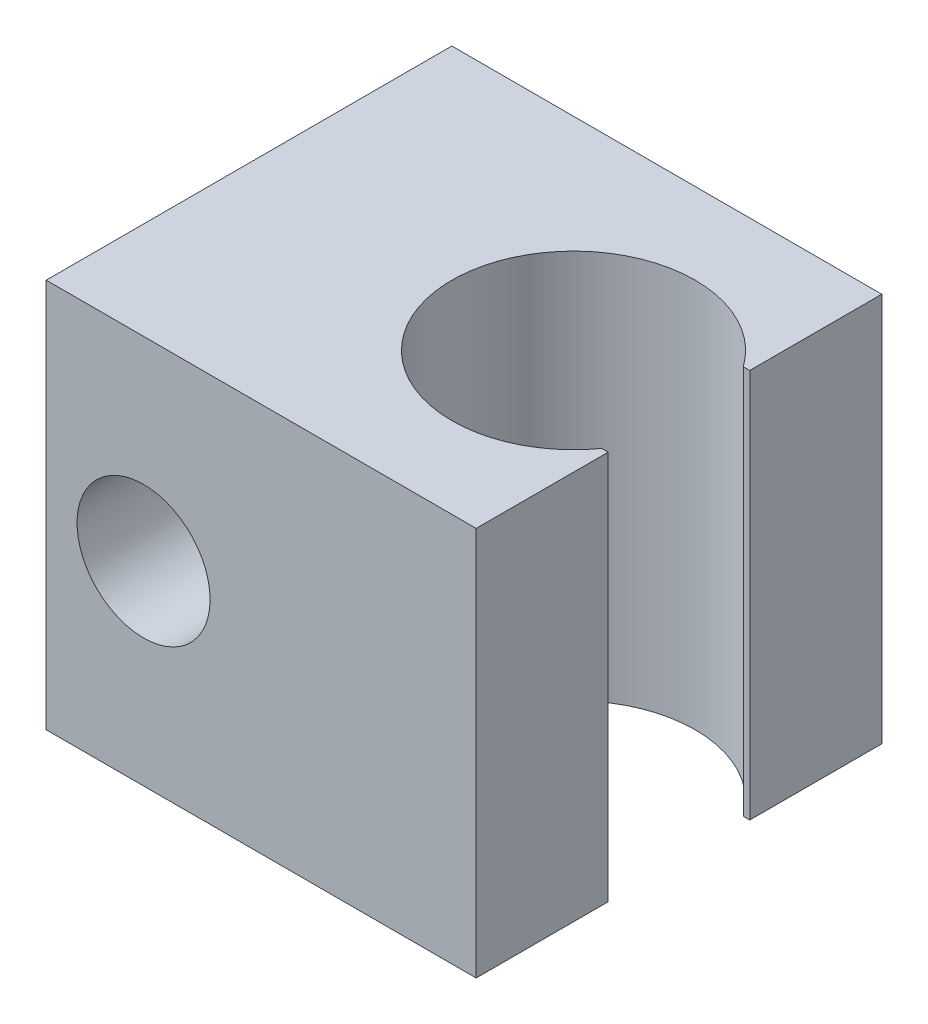
SolidWorks part; units mm, degrees
material "PET"
ref_plane "Front Plane" through (0, 0, 0) normal (0, 0, 1) x (1, 0, 0)
ref_plane "Top Plane" through (0, 0, 0) normal (0, 1, 0) x (1, 0, 0)
ref_plane "Right Plane" through (0, 0, 0) normal (1, 0, 0) x (0, 0, -1)
sketch "Sketch1" plane through (0, 0, 0) normal (0, 1, 0) x (1, 0, 0)
  line L1 (0, 12.5) -> (-10, 12.5)
  line L2 (-10, -12.5) -> (-20, -12.5)
  line L3 (0, -12.5) -> (-10, -12.5)
  line L4 (-10, 12.5) -> (-10, -12.5)
  line L5 (-10, -12.5) -> (-10, 12.5)
  line L6 (-10, 12.5) -> (-20, 12.5)
  line L7 (-20, -12.5) -> (-20, 12.5)
  line L8 (0, 12.5) -> (12.5, 12.5)
  line L10 (0, -12.5) -> (12.5, -12.5)
  line L11 (12.5, 12.5) -> (12.5, -12.5)
  circle A0 centre (0, 0) radius 7.5
  arc A1 (0, -12.5) -> (0, 12.5) centre (0, 0) ccw construction
  dimension "D1" = 15
  dimension "D2" = 12.5
  dimension "D3" = 10
  dimension "D4" = 10
extrude "Boss-Extrude1" add sketch "Sketch1" along normal blind 24 contours L3 A1 L1 L4 A0 region at (6.25, 0, -12.1637)
sketch "Sketch5" plane through (0, 0, 0) normal (0, -1, 0) x (1, 0, 0)
  line L0 (12.5, -12.5) -> (12.5, 12.5) construction
  line L1 (12.5, 12.5) -> (6.5, 12.5)
  line L2 (12.5, 12.5) -> (12.5, -12.5)
  line L3 (12.5, -12.5) -> (6.5, -12.5)
  line L4 (6.5, 12.5) -> (6.5, 4.3635)
  line L6 (6.5, -4.3635) -> (6.5, -12.5)
  line L7 (6.5, 4.3635) -> (6.1, 4.3635)
  line L8 (12.5, 12.5) -> (-10, 12.5) construction
  line L9 (6.5, -4.3635) -> (6.1, -4.3635)
  line L10 (6.1, 4.3635) -> (6.1, -4.3635)
  line L11 (12.5, -12.5) -> (-10, -12.5) construction
  circle A3 centre (0, 0) radius 7.5 construction
  point P15 (6.1, 0)
  point P16 (12.5, 0)
  dimension "D1" = 6
  dimension "D2" = 0.4
  dimension "D3" = 0
extrude "Cut-Extrude4" cut sketch "Sketch5" against normal through all
sketch "Sketch7" plane through (0, 0, 0) normal (0, -1, 0) x (1, 0, 0)
  line L1 (0, 12.5) -> (-10, 12.5)
  line L2 (-10, -12.5) -> (-20, -12.5)
  line L3 (0, -12.5) -> (-10, -12.5)
  line L4 (-10, 12.5) -> (-10, -12.5)
  line L5 (-10, -12.5) -> (-10, 12.5)
  line L6 (-10, 12.5) -> (-20, 12.5)
  line L7 (-20, -12.5) -> (-20, 12.5)
  circle A0 centre (0, 0) radius 7.5
  arc A1 (0, -12.5) -> (0, 12.5) centre (0, 0) ccw
  line M21 (-10, 12.5) -> (-10, -12.5)
  dimension "D1" = 15
  dimension "D2" = 12.5
  dimension "D3" = 10
  dimension "D4" = 10
extrude "Boss-Extrude2" add sketch "Sketch7" against normal blind 24 contours L7 L2 L6 M21 region at (-15, 0, 0)
sketch "Sketch8" plane through (0, 0, 12.5) normal (0, 0, 1) x (1, 0, 0)
  line L0 (-20, 12) -> (6.5, 12) construction
  line L1 (-20, 24) -> (-20, 0) construction
  line L3 (6.5, 24) -> (6.5, 0) construction
  circle A0 centre (-14, 12) radius 4.1
  dimension "D1" = 8.2
  dimension "D2" = 6
extrude "Cut-Extrude5" cut sketch "Sketch8" against normal blind 48
